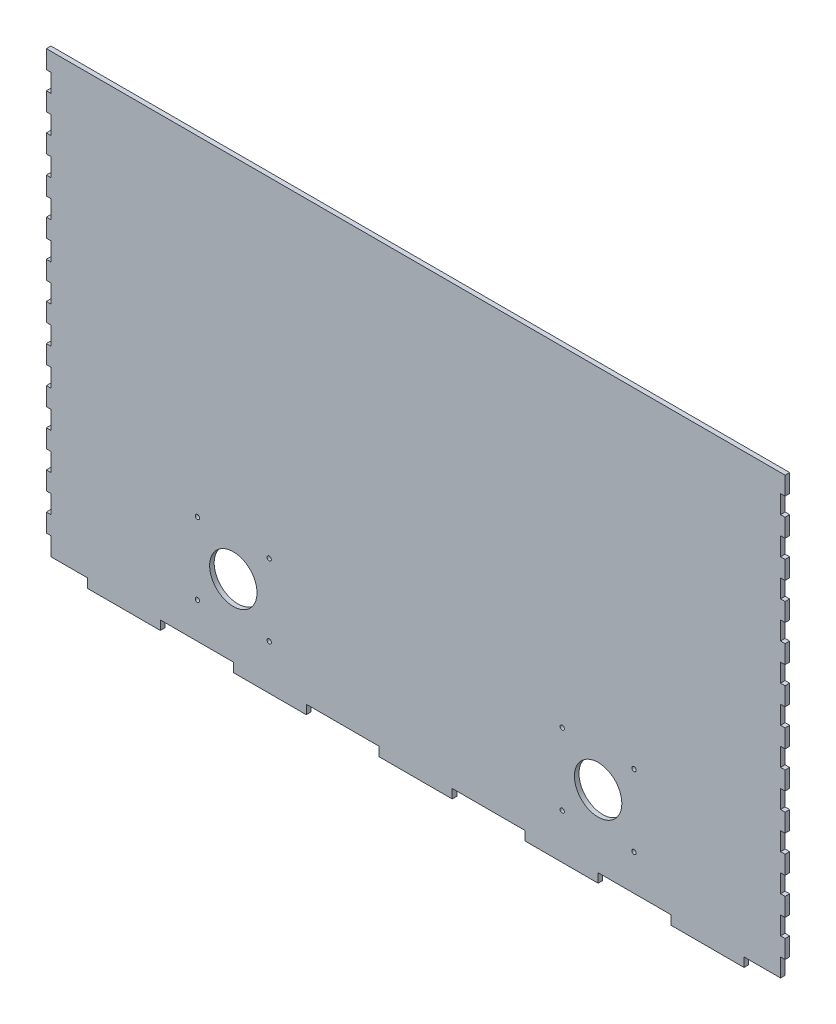
SolidWorks part; units mm, degrees
ref_plane "Front Plane" through (0, 0, 0) normal (0, 0, 1) x (1, 0, 0)
ref_plane "Top Plane" through (0, 0, 0) normal (0, 1, 0) x (1, 0, 0)
ref_plane "Right Plane" through (0, 0, 0) normal (1, 0, 0) x (0, 0, -1)
sketch "Sketch1" plane through (0, 0, 0) normal (0, 0, 1) x (1, 0, 0)
  line L0 (0, 0) -> (508, 0)
  line L1 (508, 0) -> (508, 304.8)
  line L2 (508, 304.8) -> (0, 304.8)
  line L3 (0, 304.8) -> (0, 0)
  line L4 (254, 304.8) -> (254, 0) construction
  line L5 (0, 304.8) -> (-3.175, 304.8)
  line L6 (-3.175, 304.8) -> (-3.175, 292.1)
  line L7 (-3.175, 292.1) -> (0, 292.1)
  line L8 (25.4, 0) -> (25.4, -6.35)
  line L9 (25.4, -6.35) -> (76.2, -6.35)
  line L10 (76.2, -6.35) -> (76.2, 0)
  line L13 (0, 279.4) -> (-3.175, 279.4)
  line L14 (-3.175, 279.4) -> (-3.175, 266.7)
  line L15 (-3.175, 266.7) -> (0, 266.7)
  line L17 (0, 254) -> (-3.175, 254)
  line L18 (-3.175, 254) -> (-3.175, 241.3)
  line L19 (-3.175, 241.3) -> (0, 241.3)
  line L21 (0, 228.6) -> (-3.175, 228.6)
  line L22 (-3.175, 228.6) -> (-3.175, 215.9)
  line L23 (-3.175, 215.9) -> (0, 215.9)
  line L25 (0, 203.2) -> (-3.175, 203.2)
  line L26 (-3.175, 203.2) -> (-3.175, 190.5)
  line L27 (-3.175, 190.5) -> (0, 190.5)
  line L29 (0, 177.8) -> (-3.175, 177.8)
  line L30 (-3.175, 177.8) -> (-3.175, 165.1)
  line L31 (-3.175, 165.1) -> (0, 165.1)
  line L33 (0, 152.4) -> (-3.175, 152.4)
  line L34 (-3.175, 152.4) -> (-3.175, 139.7)
  line L35 (-3.175, 139.7) -> (0, 139.7)
  line L37 (0, 127) -> (-3.175, 127)
  line L38 (-3.175, 127) -> (-3.175, 114.3)
  line L39 (-3.175, 114.3) -> (0, 114.3)
  line L41 (0, 101.6) -> (-3.175, 101.6)
  line L42 (-3.175, 101.6) -> (-3.175, 88.9)
  line L43 (-3.175, 88.9) -> (0, 88.9)
  line L45 (0, 76.2) -> (-3.175, 76.2)
  line L46 (-3.175, 76.2) -> (-3.175, 63.5)
  line L47 (-3.175, 63.5) -> (0, 63.5)
  line L49 (0, 50.8) -> (-3.175, 50.8)
  line L50 (-3.175, 50.8) -> (-3.175, 38.1)
  line L51 (-3.175, 38.1) -> (0, 38.1)
  line L53 (0, 25.4) -> (-3.175, 25.4)
  line L54 (-3.175, 25.4) -> (-3.175, 12.7)
  line L55 (-3.175, 12.7) -> (0, 12.7)
  line L57 (0, 304.8) -> (0, 279.4) construction
  line L59 (127, 0) -> (127, -6.35)
  line L60 (127, -6.35) -> (177.8, -6.35)
  line L61 (177.8, -6.35) -> (177.8, 0)
  line L63 (228.6, 0) -> (228.6, -6.35)
  line L64 (228.6, -6.35) -> (279.4, -6.35)
  line L65 (279.4, -6.35) -> (279.4, 0)
  line L67 (330.2, 0) -> (330.2, -6.35)
  line L68 (330.2, -6.35) -> (381, -6.35)
  line L69 (381, -6.35) -> (381, 0)
  line L70 (76.2, 0) -> (177.8, 0) construction
  line L72 (431.8, 0) -> (431.8, -6.35)
  line L73 (431.8, -6.35) -> (482.6, -6.35)
  line L74 (482.6, -6.35) -> (482.6, 0)
  line L76 (511.175, 12.7) -> (508, 12.7)
  line L77 (511.175, 25.4) -> (511.175, 12.7)
  line L78 (508, 25.4) -> (511.175, 25.4)
  line L80 (511.175, 38.1) -> (508, 38.1)
  line L81 (511.175, 50.8) -> (511.175, 38.1)
  line L82 (508, 50.8) -> (511.175, 50.8)
  line L84 (511.175, 63.5) -> (508, 63.5)
  line L85 (511.175, 76.2) -> (511.175, 63.5)
  line L86 (508, 76.2) -> (511.175, 76.2)
  line L88 (511.175, 88.9) -> (508, 88.9)
  line L89 (511.175, 101.6) -> (511.175, 88.9)
  line L90 (508, 101.6) -> (511.175, 101.6)
  line L92 (511.175, 114.3) -> (508, 114.3)
  line L93 (511.175, 127) -> (511.175, 114.3)
  line L94 (508, 127) -> (511.175, 127)
  line L96 (511.175, 139.7) -> (508, 139.7)
  line L97 (511.175, 152.4) -> (511.175, 139.7)
  line L98 (508, 152.4) -> (511.175, 152.4)
  line L100 (511.175, 165.1) -> (508, 165.1)
  line L101 (511.175, 177.8) -> (511.175, 165.1)
  line L102 (508, 177.8) -> (511.175, 177.8)
  line L104 (511.175, 190.5) -> (508, 190.5)
  line L105 (511.175, 203.2) -> (511.175, 190.5)
  line L106 (508, 203.2) -> (511.175, 203.2)
  line L108 (511.175, 215.9) -> (508, 215.9)
  line L109 (511.175, 228.6) -> (511.175, 215.9)
  line L110 (508, 228.6) -> (511.175, 228.6)
  line L112 (511.175, 241.3) -> (508, 241.3)
  line L113 (511.175, 254) -> (511.175, 241.3)
  line L114 (508, 254) -> (511.175, 254)
  line L116 (511.175, 266.7) -> (508, 266.7)
  line L117 (511.175, 279.4) -> (511.175, 266.7)
  line L118 (508, 279.4) -> (511.175, 279.4)
  line L120 (511.175, 292.1) -> (508, 292.1)
  line L121 (511.175, 304.8) -> (511.175, 292.1)
  line L122 (508, 304.8) -> (511.175, 304.8)
  dimension "D1" = 508
  dimension "D2" = 304.8
  dimension "D3" = 3.175
  dimension "D4" = 12.7
  dimension "D5" = 6.35
  dimension "D6" = 50.8
  dimension "D7" = 25.4
  dimension "D9" = 25.4
  dimension "D11" = 101.6
  dimension "D8" = 12
  dimension "D10" = 5
extrude "Boss-Extrude1" add sketch "Sketch1" along normal blind 3.175 contours L2 L3 L0 L1 | L9 L10 L0 L8 | L60 L61 L0 L59 | L64 L65 L0 L63 | L68 L69 L0 L67 | L73 L74 L0 L72 | L54 L55 L3 L53 | L50 L51 L3 L49 | L46 L47 L3 L45 | L42 L43 L3 L41 | L38 L39 L3 L37 | L34 L35 L3 L33 | L30 L31 L3 L29 | L26 L27 L3 L25 | L22 L23 L3 L21 | L18 L19 L3 L17 | L14 L15 L3 L13 | L6 L7 L3 L5 | L78 L1 L76 L77 | L82 L1 L80 L81 | L86 L1 L84 L85 | L90 L1 L88 L89 | L98 L1 L96 L97 | L94 L1 L92 L93 | L102 L1 L100 L101 | L106 L1 L104 L105 | L110 L1 L108 L109 | L114 L1 L112 L113 | L118 L1 L116 L117 | L122 L1 L120 L121 region at (254, 152.4, 0) region at (50.8, -3.175, 0) region at (-1.5875, 19.05, 0) region at (152.4, -3.175, 0) region at (-1.5875, 44.45, 0) region at (254, -3.175, 0) region at (-1.5875, 69.85, 0) region at (355.6, -3.175, 0) region at (-1.5875, 95.25, 0) region at (457.2, -3.175, 0) region at (-1.5875, 120.65, 0) region at (-1.5875, 146.05, 0) region at (509.5875, 19.05, 0) region at (-1.5875, 171.45, 0) region at (509.5875, 44.45, 0) region at (-1.5875, 196.85, 0) region at (509.5875, 69.85, 0) region at (-1.5875, 222.25, 0) region at (509.5875, 95.25, 0) region at (-1.5875, 247.65, 0) region at (509.5875, 120.65, 0) region at (-1.5875, 273.05, 0) region at (509.5875, 146.05, 0) region at (-1.5875, 298.45, 0) region at (509.5875, 171.45, 0) region at (509.5875, 298.45, 0) region at (509.5875, 196.85, 0) region at (509.5875, 273.05, 0) region at (509.5875, 222.25, 0) region at (509.5875, 247.65, 0)
sketch "Sketch2" plane through (0, 0, 3.175) normal (0, 0, 1) x (1, 0, 0)
  line L0 (254, 304.8) -> (254, -6.35) construction
  line L1 (511.175, 304.8) -> (-3.175, 304.8) construction
  line L2 (228.6, -6.35) -> (279.4, -6.35) construction
  line L3 (0, 6.35) -> (254, 6.35) construction
  line L5 (0, 12.7) -> (0, 0) construction
  line L6 (127, 6.35) -> (127, 304.8) construction
  line L7 (110.5, 50) -> (143.5, 50) construction
  line L8 (76.2, 0) -> (127, 0) construction
  circle A0 centre (127, 50) radius 16.5
  circle A1 centre (102, 75) radius 1.5
  circle A2 centre (152, 75) radius 1.5
  circle A3 centre (152, 25) radius 1.5
  circle A4 centre (102, 25) radius 1.5
  circle A5 centre (381, 50) radius 16.5
  circle A6 centre (356, 75) radius 1.5
  circle A7 centre (356, 25) radius 1.5
  circle A8 centre (406, 25) radius 1.5
  circle A9 centre (406, 75) radius 1.5
  dimension "D1" = 33
  dimension "D2" = 3
  dimension "D3" = 25
  dimension "D4" = 25
  dimension "D5" = 50
extrude "Cut-Extrude1" cut sketch "Sketch2" against normal up to surface (3.175 mm away) up to face at (254, 125.5767, 0)
equation "\"wall_thickness\" = 0.125in"
equation "\"base_thickness\" = 0.25in"
equation "\"D3@Sketch1\"=\"wall_thickness\""
equation "\"D5@Sketch1\"=\"base_thickness\""
equation "\"D1@Boss-Extrude1\"=\"wall_thickness\""
